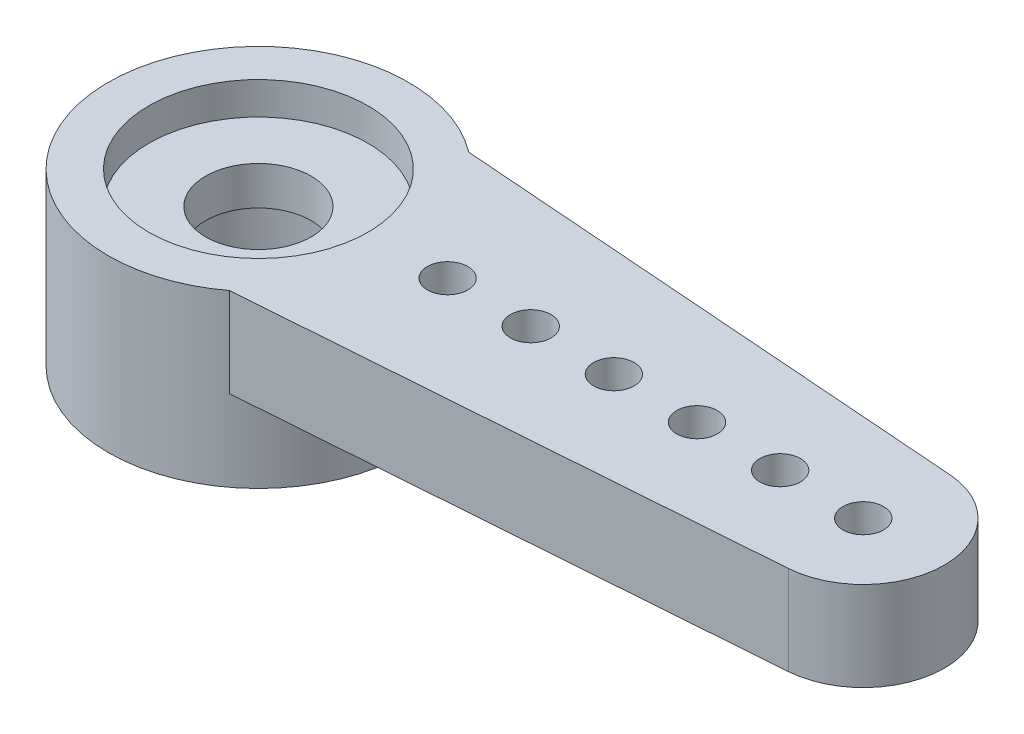
SolidWorks part; units mm, degrees
material "PA Type 6"
ref_plane "Front Plane" through (0, 0, 0) normal (0, 0, 1) x (1, 0, 0)
ref_plane "Top Plane" through (0, 0, 0) normal (0, 1, 0) x (1, 0, 0)
ref_plane "Right Plane" through (0, 0, 0) normal (1, 0, 0) x (0, 0, -1)
ref_axis "X-Axis" through (-88.99, 0, 0) along (1, 0, 0)
ref_axis "Y-Axis" through (0, 0, -88.99) along (0, 0, 1)
ref_axis "Z-Axis" through (0, 55, 0) along (0, -1, 0)
sketch "Sketch2" plane through (0, 0, 0) normal (0, 0, 1) x (1, 0, 0)
  line L0 (0, 0) -> (0, -2) construction
  line L1 (2.7, 2.2) -> (2.7, 1.4)
  line L2 (2.7, 1.4) -> (1.3, 1.4)
  line L3 (1.3, 1.4) -> (1.3, 0.45)
  line L4 (1.3, 0.45) -> (2.35, 0.45)
  line L5 (2.35, 0.45) -> (2.35, -2)
  line L6 (2.35, -2) -> (3.7, -2)
  line L7 (3.7, -2) -> (3.7, 2.2)
  line L8 (3.7, 2.2) -> (2.7, 2.2)
  dimension "D1" = 4.7
  dimension "D2" = 2.6
  dimension "D3" = 5.4
  dimension "D4" = 0.8
  dimension "D5" = 7.4
  dimension "D6" = 2
  dimension "D7" = 2.45
  dimension "D8" = 4.2
revolve "Revolve1" add sketch "Sketch2" angle 360 about axis through (0, 55, 0) along (0, -1, 0)
sketch "Sketch3" plane through (0, 0, 0) normal (0, 1, 0) x (1, 0, 0)
  line L0 (2.2333, -2.95) -> (15.0487, -1.9945)
  line L1 (0, 0) -> (20.2296, 0) construction
  line L2 (-3.7, 0) -> (16.9, 0) construction
  line L3 (2.2333, -2.95) -> (2.2333, 0)
  line L4 (2.2333, 0) -> (16.9, 0)
  circle A0 centre (0, 0) radius 3.7 construction
  circle A1 centre (14.9, 0) radius 2
  circle A2 centre (0, 0) radius 3.7
  circle A3 centre (14.9, 0) radius 0.5
  circle A4 centre (12.8521, 0) radius 0.5
  circle A5 centre (10.8042, 0) radius 0.5
  circle A6 centre (8.7562, 0) radius 0.5
  circle A7 centre (6.7083, 0) radius 0.5
  circle A8 centre (4.6604, 0) radius 0.5
  dimension "D2" = 4
  dimension "D5" = 6
  dimension "D1" = 2.95
  dimension "D4" = 1
  dimension "D3" = 20.6
  dimension "D6" = 2.0479
extrude "Boss-Extrude1" add sketch "Sketch3" along normal up to surface (2.2 mm away) contours A8 L4 A2 L0 A1 A4 A5 A6 A7 | A4 A1 L4 A3 region at (8.0476, 0, 1.4026) region at (14.951, 0, 0.9109) up to face at (0, 2.2, 2.7)
mirror "Mirror1" about plane through (0, 17.1605, 0) normal (0, 0, -1) of "Boss-Extrude1"
